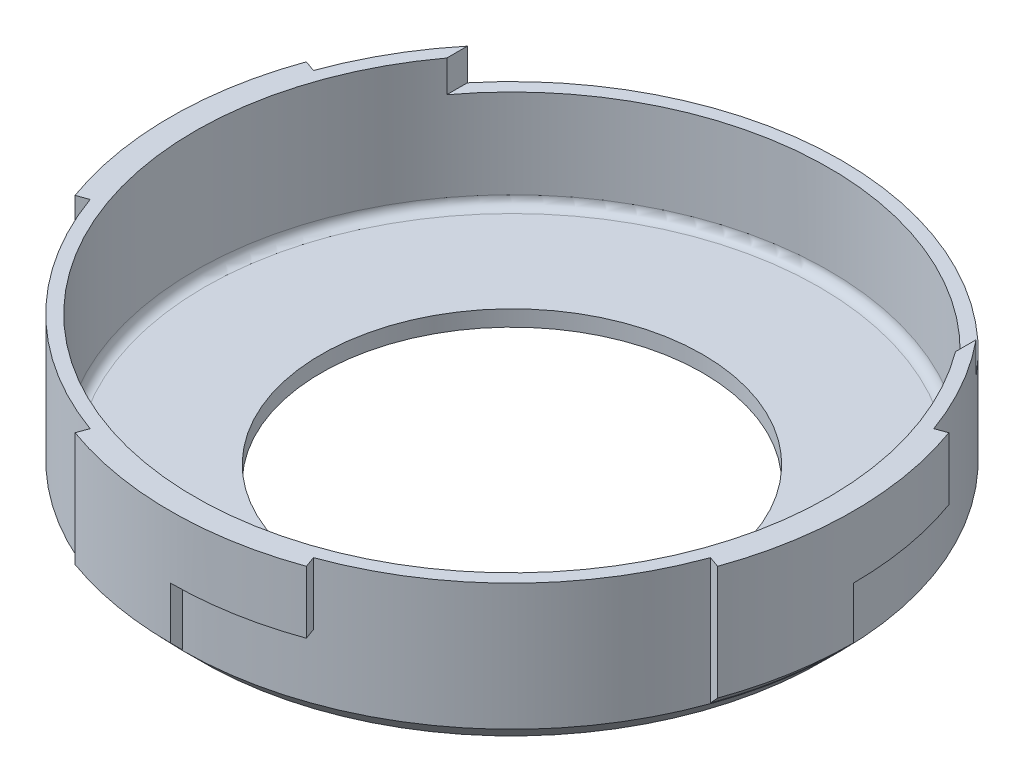
SolidWorks part; units mm, degrees
material "Nylon-CF-10%"
ref_plane "Front Plane" through (0, 0, 0) normal (0, 0, 1) x (1, 0, 0)
ref_plane "Top Plane" through (0, 0, 0) normal (0, 1, 0) x (1, 0, 0)
ref_plane "Right Plane" through (0, 0, 0) normal (1, 0, 0) x (0, 0, -1)
sketch "Sketch1" plane through (0, 0, 0) normal (0, 1, 0) x (1, 0, 0)
  circle A0 centre (0, 0) radius 51.85
  circle A1 centre (0, 0) radius 30
  dimension "D1" = 103.7
  dimension "D2" = 60
extrude "Boss-Extrude1" add sketch "Sketch1" along normal blind 2.5
sketch "Sketch2" plane through (0, 2.5, 0) normal (0, 1, 0) x (1, 0, 0)
  circle A0 centre (0, 0) radius 49.85
  circle A1 centre (0, 0) radius 51.85
  dimension "D1" = 2
extrude "Boss-Extrude2" add sketch "Sketch2" along normal blind 20
sketch "Sketch3" plane through (0, 0, 0) normal (0, 0, 1) x (1, 0, 0)
  line L0 (51.85, 22.5) -> (-51.85, 22.5) construction
  line L1 (51.85, 22.5) -> (-51.85, 22.5) construction
  line L2 (0, -6.2492) -> (0, 36.3111) construction
  line L3 (51.85, 22.5) -> (53.7, 22.5)
  line L4 (51.85, 22.5) -> (51.85, 2.7)
  line L5 (51.85, 2.7) -> (53.7, 2.7)
  line L6 (53.7, 22.5) -> (53.7, 2.7)
  dimension "D1" = 1.85
  dimension "D2" = 19.8
revolve "Revolve1" add sketch "Sketch3" angle 19.8 about L2 reverse direction yes
sketch "Sketch4" plane through (0, 0, 0) normal (0, 0, 1) x (1, 0, 0)
  line L0 (51.85, 22.5) -> (51.85, 2.7) construction
  line L1 (53.7, 22.5) -> (51.85, 22.5)
  line L2 (53.7, 22.5) -> (53.7, 12.7)
  line L3 (53.7, 12.7) -> (51.85, 12.7)
  line L4 (51.85, 22.5) -> (51.85, 12.7)
  line L5 (0, 0) -> (0, 24.9806) construction
  dimension "D1" = 9.8
revolve "Revolve2" add sketch "Sketch4" angle 19.8 about L5
pattern_circular "CirPattern1" count 3 every 90 about axis through (0, 22.5, 0) along (0, -1, 0) of "Revolve2", "Revolve1"
sketch "Sketch5" plane through (0, 0, 0) normal (0, 0, 1) x (1, 0, 0)
  line L0 (0, -5.565) -> (0, 31.5917) construction
  line L1 (48.7847, 22.5) -> (-48.7847, 22.5) construction
  line L2 (40, 22.5) -> (-40, 22.5)
  line L3 (40, 22.5) -> (40, 17.5)
  line L4 (40, 17.5) -> (-40, 17.5)
  line L5 (-40, 22.5) -> (-40, 17.5)
  point P7 (0, 17.5)
  dimension "D1" = 5
  dimension "D2" = 80
extrude "Cut-Extrude1" cut sketch "Sketch5" against normal through all
sketch "Sketch6" plane through (0, 0, 0) normal (0, -1, 0) x (1, 0, 0)
  circle A0 centre (0, 0) radius 51.85
  circle A1 centre (0, 0) radius 30
extrude "Boss-Extrude3" add sketch "Sketch6" along normal blind 0.5
sketch "Sketch7" plane through (0, 2.5, 0) normal (0, 1, 0) x (1, 0, 0)
  circle A0 centre (0, 0) radius 30 construction
  circle A1 centre (0, 0) radius 49.85
  circle A2 centre (0, 0) radius 49.85
  circle A3 centre (0, 0) radius 30
  dimension "D1" = 0
extrude "Cut-Extrude2" cut sketch "Sketch7" against normal blind 0.5
fillet "Fillet1" radius 1.5 1 edges at (0, 2, 49.85)
chamfer "Chamfer1" distance 3.1 angle 45 1 edges at (0, -0.5, -51.85)
chamfer "Chamfer2" distance 1.85 angle 45 3 edges at (-9.2326, 2.7, 52.9004) (52.9004, 2.7, 9.2326) (-52.9004, 2.7, -9.2326)
